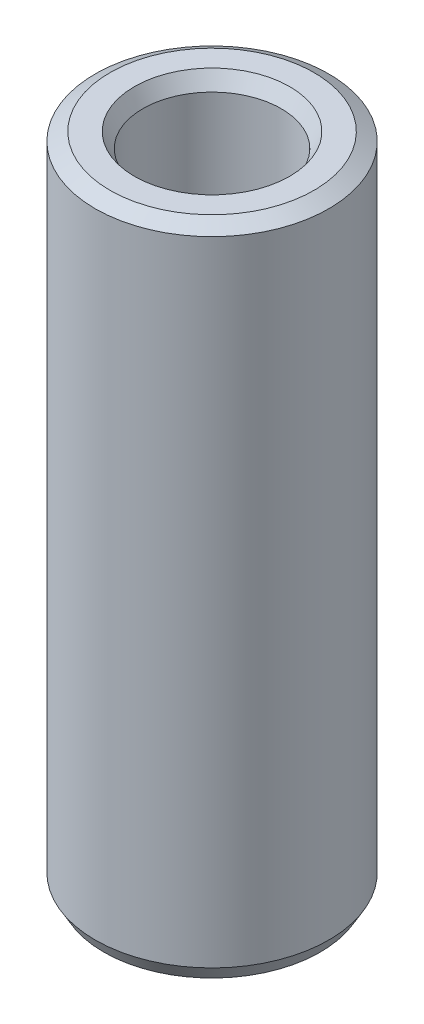
SolidWorks part; units mm, degrees
ref_plane "Front Plane" through (0, 0, 0) normal (0, 0, 1) x (1, 0, 0)
ref_plane "Top Plane" through (0, 0, 0) normal (0, 1, 0) x (1, 0, 0)
ref_plane "Right Plane" through (0, 0, 0) normal (1, 0, 0) x (0, 0, -1)
sketch "Sketch1" plane through (0, 0, 0) normal (0, 1, 0) x (1, 0, 0)
  circle A0 centre (0, 0) radius 37.5
  dimension "SLEEVE_OD" = 75
extrude "Boss-Extrude1" add sketch "Sketch1" along normal blind 210.7993
sketch "Sketch2" plane through (0, 0, 0) normal (0, 1, 0) x (1, 0, 0)
  circle A0 centre (0, 0) radius 22.2029
  dimension "BORE_D" = 44.4058
extrude "Cut-Extrude1" cut sketch "Sketch2" along normal through all
chamfer "Chamfer1" distance 2.7394 angle 60 4 edges at (0, 210.7993, 22.2029) (0, 0, 22.2029) (0, 0, 37.5) (0, 210.7993, 37.5) first distance on face at (0, 210.7993, 22.2029) first distance on face at (0, 0, 22.2029) first distance on face at (0, 210.7993, 37.5)
